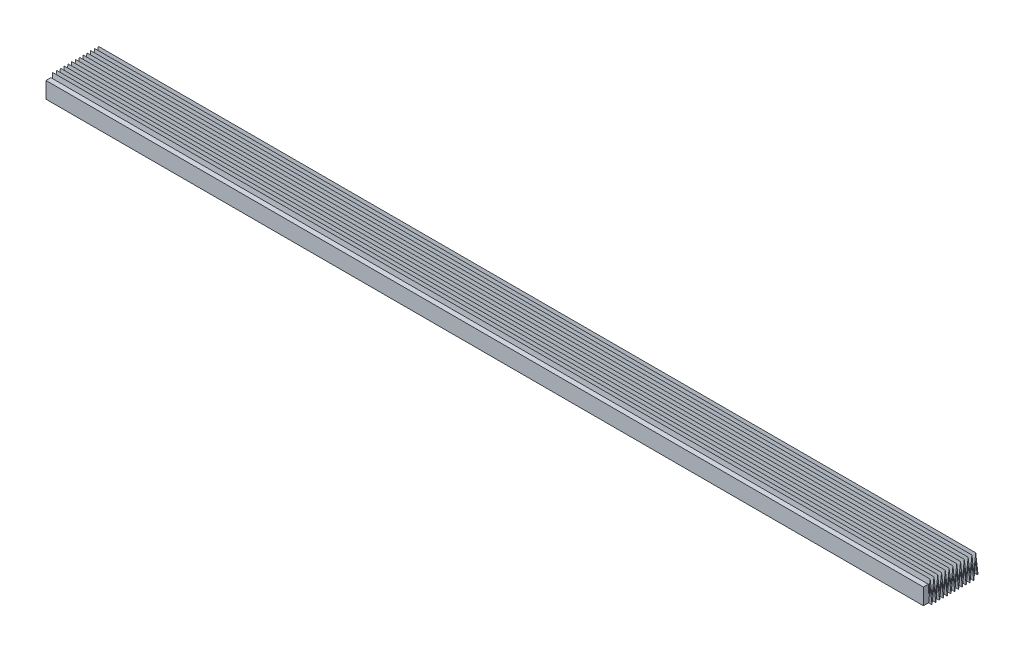
SolidWorks part; units mm, degrees
ref_plane "Front Plane" through (0, 0, 0) normal (0, 0, 1) x (1, 0, 0)
ref_plane "Top Plane" through (0, 0, 0) normal (0, 1, 0) x (1, 0, 0)
ref_plane "Right Plane" through (0, 0, 0) normal (1, 0, 0) x (0, 0, -1)
sketch "Sketch2" plane through (0, 0, 0) normal (0, 0, 1) x (1, 0, 0)
  line L1 (-270, 10) -> (270, 10)
  line L2 (-270, 10) -> (-270, 0)
  line L3 (-270, 0) -> (270, 0)
  line L4 (270, 10) -> (270, 0)
  point P4 (0, 0)
  dimension "D1" = 10
  dimension "D2" = 540
extrude "Boss-Extrude1" add sketch "Sketch2" along normal blind 3
sketch "Sketch3" plane through (270, 0, 0) normal (1, 0, 0) x (0, 0, -1)
  line L0 (0, 10) -> (30.3713, 10) construction
  line L1 (0, 0) -> (30.3713, 0) construction
  line L3 (0, 0) -> (1.1681, 10)
  line L4 (1.1681, 10) -> (2.3363, 0)
  line L5 (2.3363, 0) -> (3.5044, 10)
  line L6 (3.5044, 10) -> (4.6725, 0)
  line L7 (4.6725, 0) -> (5.8406, 10)
  line L8 (5.8406, 10) -> (7.0088, 0)
  line L9 (7.0088, 0) -> (8.1769, 10)
  line L10 (8.1769, 10) -> (9.345, 0)
  line L11 (9.345, 0) -> (10.5131, 10)
  line L12 (10.5131, 10) -> (11.6813, 0)
  line L13 (11.6813, 0) -> (12.8494, 10)
  line L14 (12.8494, 10) -> (14.0175, 0)
  line L15 (14.0175, 0) -> (15.1856, 10)
  line L16 (15.1856, 10) -> (16.3538, 0)
  line L17 (16.3538, 0) -> (17.5219, 10)
  line L18 (17.5219, 10) -> (18.69, 0)
  line L20 (18.69, 0) -> (19.8581, 10)
  line L21 (19.8581, 10) -> (21.0263, 0)
  line L22 (21.0263, 0) -> (22.1944, 10)
  line L23 (22.1944, 10) -> (23.3625, 0)
  line L24 (23.3625, 0) -> (24.5307, 10)
  line L25 (24.5307, 10) -> (25.6988, 0)
  line L26 (25.6988, 0) -> (26.8669, 10)
  line L27 (26.8669, 10) -> (28.035, 0)
  line L28 (28.035, 0) -> (29.2032, 10)
  line L29 (29.2032, 10) -> (30.3713, 0)
  line L30 (30.3713, 10) -> (30.3713, 0) construction
  line L32 (30.3713, 10) -> (30.3713, 0) construction
extrude "Extrude-Thin1" add sketch "Sketch3" against normal through all thin thin type mid plane wall 0.5
